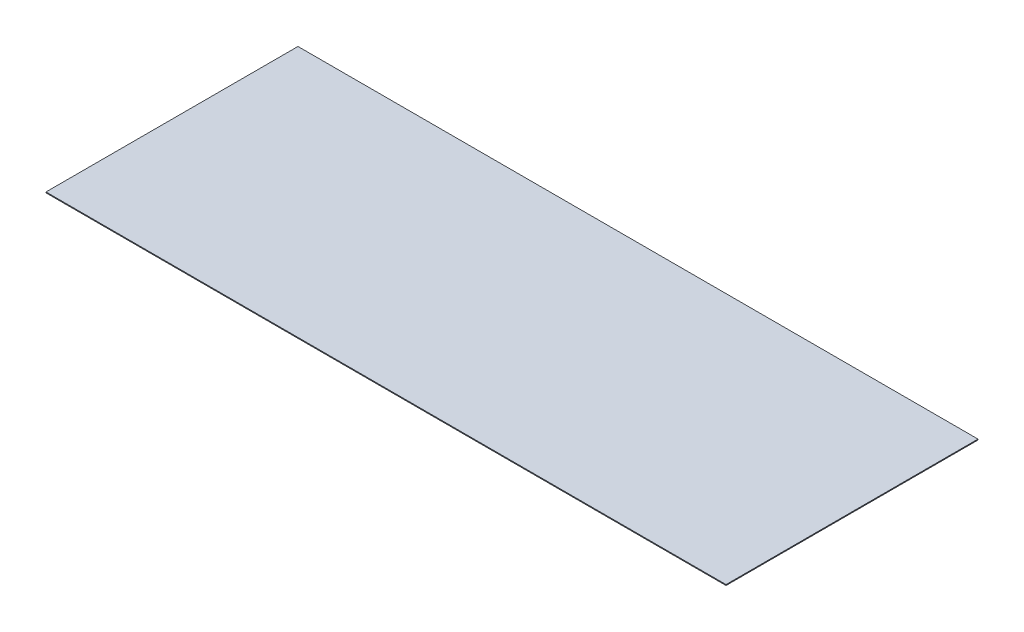
SolidWorks part; units mm, degrees
ref_plane "Front Plane" through (0, 0, 0) normal (0, 0, 1) x (1, 0, 0)
ref_plane "Top Plane" through (0, 0, 0) normal (0, 1, 0) x (1, 0, 0)
ref_plane "Right Plane" through (0, 0, 0) normal (1, 0, 0) x (0, 0, -1)
sketch "Sketch1" plane through (0, 0, 0) normal (0, 1, 0) x (1, 0, 0)
  line L0 (-239.335, -88.68) -> (239.335, -88.68)
  line L1 (-239.335, -88.68) -> (-239.335, 88.68)
  line L2 (239.335, -88.68) -> (239.335, 88.68)
  line L3 (-239.335, 88.68) -> (239.335, 88.68)
  line L4 (-239.335, -88.68) -> (239.335, 88.68) construction
  line L5 (239.335, -88.68) -> (-239.335, 88.68) construction
  point P1 (0, 0)
  dimension "D1" = 177.36
  dimension "D2" = 478.67
extrude "Boss-Extrude1" add sketch "Sketch1" along normal blind 0.6096
